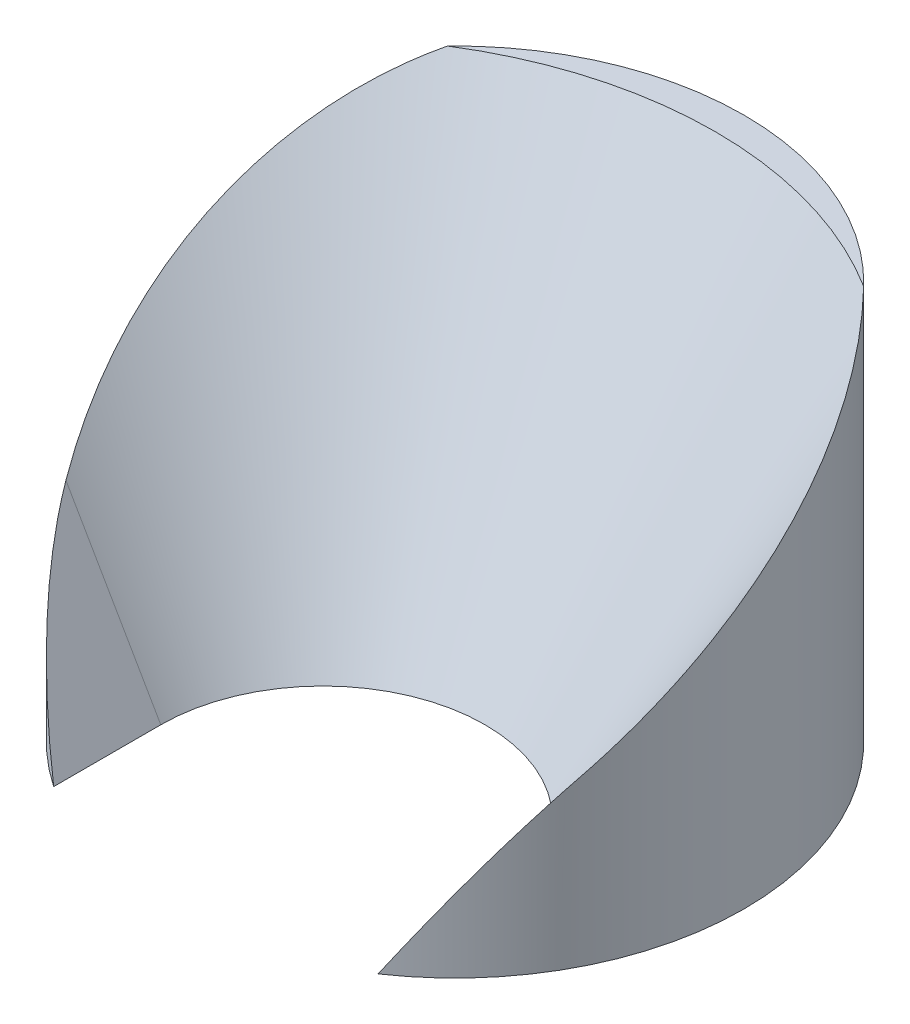
SolidWorks part; units mm, degrees
material "Teak"
ref_plane "Front Plane" through (0, 0, 0) normal (0, 0, 1) x (1, 0, 0)
ref_plane "Top Plane" through (0, 0, 0) normal (0, 1, 0) x (1, 0, 0)
ref_plane "Right Plane" through (0, 0, 0) normal (1, 0, 0) x (0, 0, -1)
sketch "Sketch1" plane through (0, 0, 0) normal (0, 1, 0) x (1, 0, 0)
  line L0 (10, -8.415) -> (10, -15.4633)
  line L1 (-10, -8.415) -> (-10, -15.4633)
  circle A0 centre (0, 0) radius 18.415
  circle A1 centre (0, -8.415) radius 10
  point P5 (-10, -8.415)
  point P6 (10, -8.415)
  dimension "D1" = 20
  dimension "D2" = 36.83
  dimension "D3" = 8.415
extrude "Boss-Extrude1" add sketch "Sketch1" along normal blind 25.4 contours A1 L0 A0 L1 region at (0, 0, -4.1316)
chamfer "Chamfer1" distance 15 angle 60 3 edges at (10, 25.4, 11.9391) (-10, 25.4, 11.9391) (0, 25.4, -1.585) first distance on face at (0, 25.4, 0.9696)
